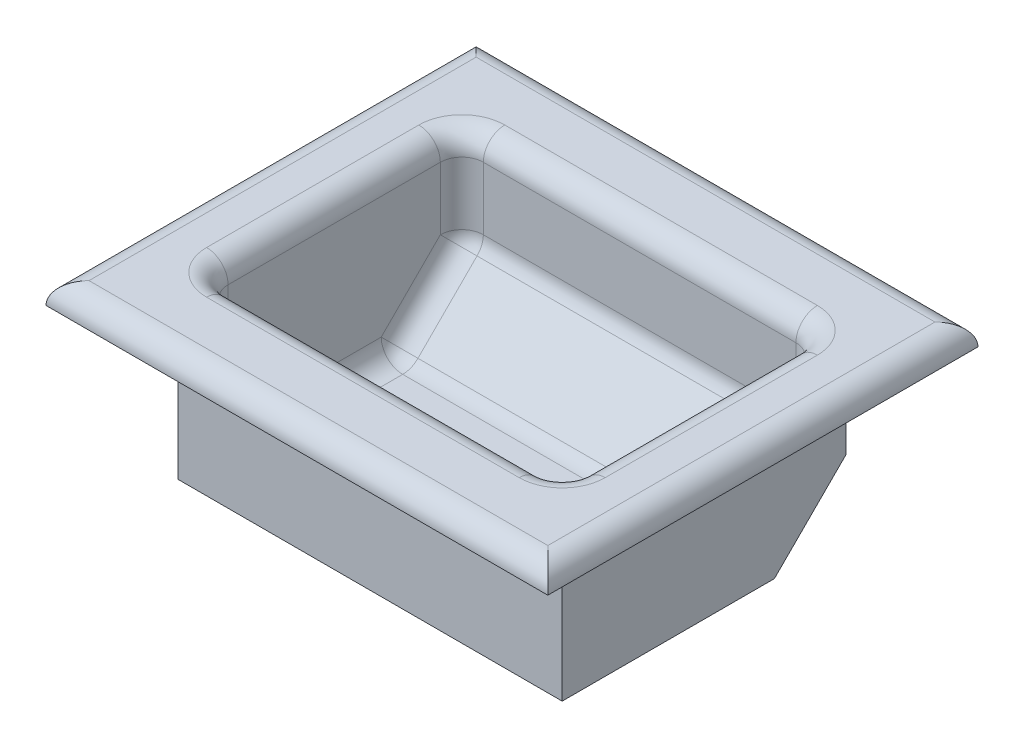
SolidWorks part; units mm, degrees
ref_plane "Спереди" through (0, 0, 0) normal (0, 0, 1) x (1, 0, 0)
ref_plane "Сверху" through (0, 0, 0) normal (0, 1, 0) x (1, 0, 0)
ref_plane "Справа" through (0, 0, 0) normal (1, 0, 0) x (0, 0, -1)
sketch "Sketch1" plane through (0, 0, 0) normal (0, 1, 0) x (1, 0, 0)
  line L1 (26.8, -19.8) -> (-26.8, -19.8)
  line L2 (26.8, -19.8) -> (26.8, 19.8)
  line L3 (26.8, 19.8) -> (-26.8, 19.8)
  line L4 (-26.8, -19.8) -> (-26.8, 19.8)
  line L5 (26.8, -19.8) -> (-26.8, 19.8) construction
  line L6 (26.8, 19.8) -> (-26.8, -19.8) construction
  point P0 (0, 0)
  dimension "D1" = 53.6
  dimension "D2" = 39.6
extrude "Boss-Extrude1" add sketch "Sketch1" along normal blind 2
sketch "Sketch2" plane through (0, 2, 0) normal (0, 1, 0) x (1, 0, 0)
  line L1 (26.8, -19.8) -> (-26.8, -19.8)
  line L2 (26.8, -19.8) -> (26.8, 19.8)
  line L3 (26.8, 19.8) -> (-26.8, 19.8)
  line L4 (-26.8, -19.8) -> (-26.8, 19.8)
  line L5 (26.8, -19.8) -> (-26.8, 19.8) construction
  line L6 (26.8, 19.8) -> (-26.8, -19.8) construction
  line L7 (24.8, -17.8) -> (-24.8, -17.8)
  line L8 (24.8, -17.8) -> (24.8, 17.8)
  line L9 (24.8, 17.8) -> (-24.8, 17.8)
  line L10 (-24.8, -17.8) -> (-24.8, 17.8)
  line L11 (24.8, -17.8) -> (-24.8, 17.8) construction
  line L12 (24.8, 17.8) -> (-24.8, -17.8) construction
  point P0 (0, 0)
  point P7 (0, 0)
  dimension "D1" = 2
  dimension "D2" = 2
extrude "Boss-Extrude2" add sketch "Sketch2" along normal blind 20
sketch "Sketch3" plane through (0, 22, 0) normal (0, 1, 0) x (1, 0, 0)
  line L1 (24.8, -17.8) -> (-24.8, -17.8)
  line L2 (24.8, -17.8) -> (24.8, 17.8)
  line L3 (24.8, 17.8) -> (-24.8, 17.8)
  line L4 (-24.8, -17.8) -> (-24.8, 17.8)
  line L5 (24.8, -17.8) -> (-24.8, 17.8) construction
  line L6 (24.8, 17.8) -> (-24.8, -17.8) construction
  line L7 (35, -30) -> (-35, -30)
  line L8 (35, -30) -> (35, 30)
  line L9 (35, 30) -> (-35, 30)
  line L10 (-35, -30) -> (-35, 30)
  line L11 (35, -30) -> (-35, 30) construction
  line L12 (35, 30) -> (-35, -30) construction
  point P0 (0, 0)
  point P7 (0, 0)
  dimension "D1" = 70
  dimension "D2" = 60
extrude "Boss-Extrude3" add sketch "Sketch3" along normal blind 3
chamfer "Chamfer1" distance 10 angle 45 2 edges at (0, 0, -19.8) (0, 2, -17.8)
fillet "Fillet1" radius 3 19 edges at (24.8, 13.5, 17.8) (0, 25, 17.8) (-24.8, 13.5, 17.8) (0, 2, 17.8) (24.8, 18.5, -17.8) (-24.8, 18.5, -17.8) (24.8, 2, 5) (-24.8, 2, 5) (24.8, 25, 0) (0, 25, -17.8) (-24.8, 25, 0) (0, 25, 30) (0, 25, -30) (35, 25, 0) (-35, 25, 0) (0, 12, -17.8) (24.8, 7, -12.8) (-24.8, 7, -12.8) (0, 2, -7.8)
